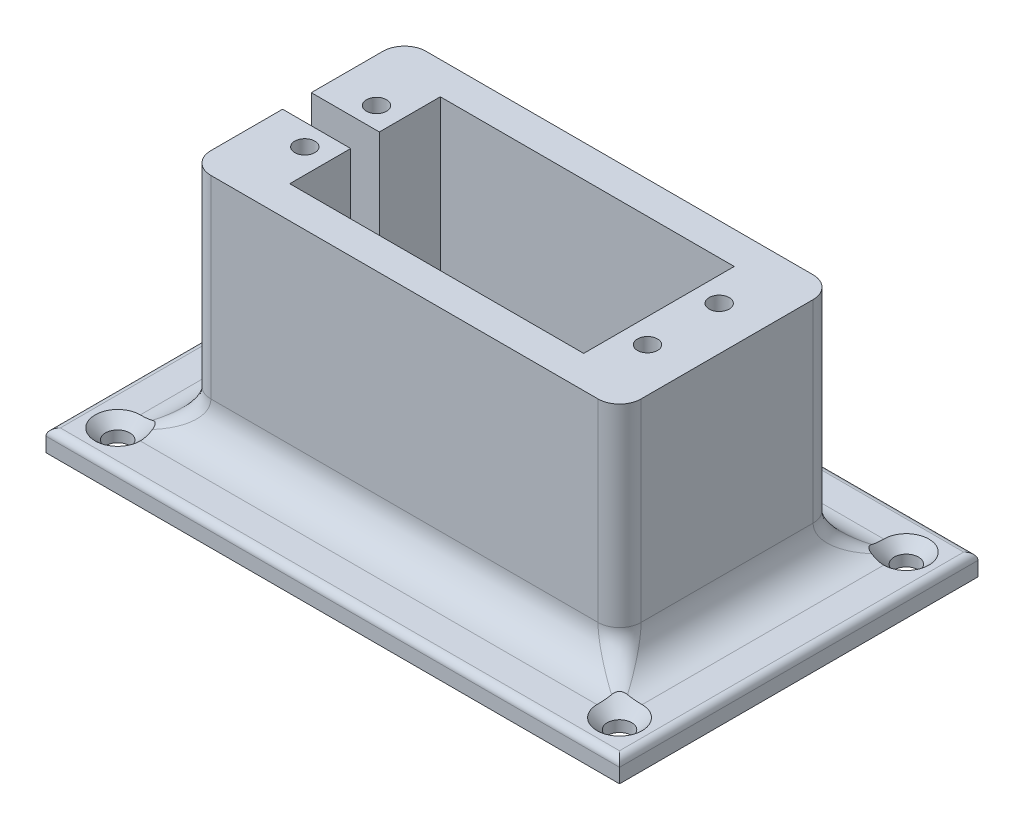
SolidWorks part; units mm, degrees
note: The reader was unsure of these and kept them because the rebuilt part matched: shared geometry of "Sketch1<4>", "Sketch1<5>".
ref_plane "Front Plane" through (0, 0, 0) normal (0, 0, 1) x (1, 0, 0)
ref_plane "Top Plane" through (0, 0, 0) normal (0, 1, 0) x (1, 0, 0)
ref_plane "Right Plane" through (0, 0, 0) normal (1, 0, 0) x (0, 0, -1)
sketch "Sketch1" plane through (0, 0, 0) normal (0, 1, 0) x (1, 0, 0)
  line L8 (0, 15) -> (60, 15) construction
  line L9 (0, 0) -> (60, 0)
  line L10 (0, 0) -> (0, 30)
  line L11 (0, 30) -> (60, 30)
  line L12 (60, 0) -> (60, 30)
  line L13 (30, 30) -> (30, 0) construction
  line L15 (9.5, 4.5) -> (50.5, 4.5)
  line L16 (9.5, 4.5) -> (9.5, 25.5)
  line L17 (9.5, 25.5) -> (50.5, 25.5)
  line L18 (50.5, 4.5) -> (50.5, 25.5)
  line L19 (9.5, 4.5) -> (50.5, 25.5) construction
  line L20 (9.5, 25.5) -> (50.5, 4.5) construction
  line L21 (-10, -10) -> (70, -10)
  line L22 (-10, -10) -> (-10, 40)
  line L23 (-10, 40) -> (70, 40)
  line L24 (70, -10) -> (70, 40)
  line L25 (-10, -10) -> (70, 40) construction
  line L26 (-10, 40) -> (70, -10) construction
  circle A0 centre (6.1, 20) radius 1.4
  circle A1 centre (53.9, 20) radius 1.4
  circle A2 centre (53.9, 10) radius 1.4
  circle A3 centre (6.1, 10) radius 1.4
  point P11 (30, 15)
  point P18 (30, 15)
  point P23 (30, 15)
  point P29 (0, 0)
  point P33 (0, 0)
  point P34 (0, 0)
  point P35 (0, 0)
  point P36 (0, 0)
  point P37 (0, 0)
  point P38 (0, 0)
  point P39 (0, 0)
  dimension "D3" = 2.8
  dimension "D1" = 60
  dimension "D2" = 30
  dimension "D4" = 10
  dimension "D5" = 47.8
  dimension "D6" = 41
  dimension "D7" = 21
  dimension "D8" = 50
  dimension "D9" = 80
extrude "Boss-Extrude2" add sketch "Sketch1" along normal blind 3 contours L21 L24 L23 L22 L12 L9 L10 L11
extrude "Boss-Extrude3" add sketch "Sketch1<4>" along normal blind 35 contours L9 L12 L11 L10 A1 A0 L18 L15 L16 L17 A2 A3
sketch "Sketch1<4>" plane through (0, 0, 0) normal (0, 1, 0) x (1, 0, 0) same geometry as "Sketch1"
extrude "Boss-Extrude4" add sketch "Sketch1<5>" along normal blind 25 contours A3 | A0 | A2 | A1
sketch "Sketch1<5>" plane through (0, 0, 0) normal (0, 1, 0) x (1, 0, 0) same geometry as "Sketch1"
sketch "Sketch2" plane through (0, 0, 0) normal (-1, 0, 0) x (0, 0, 1)
  line L0 (-17, 35) -> (-17, 12)
  line L1 (0, 35) -> (-30, 35) construction
  line L2 (-17, 12) -> (-18, 11)
  line L3 (-18, 11) -> (-18, 3)
  line L4 (0, 3) -> (-30, 3) construction
  line L5 (-15, 35) -> (-15, 3) construction
  line L6 (-12, 11) -> (-12, 3)
  line L7 (-13, 12) -> (-12, 11)
  line L8 (-13, 35) -> (-13, 12)
  line L9 (-17, 35) -> (-13, 35)
  line L10 (-18, 3) -> (-12, 3)
  dimension "D1" = 4
  dimension "D2" = 6
  dimension "D3" = 135
  dimension "D4" = 8
extrude "Cut-Extrude1" cut sketch "Sketch2" against normal up to next
sketch "Sketch8" plane through (0, 3, 0) normal (0, 1, 0) x (1, 0, 0)
  line L0 (-10, 40) -> (0, 30) construction
  line L1 (70, 40) -> (60, 30) construction
  line L2 (60, 0) -> (70, -10) construction
  line L3 (0, 0) -> (-10, -10) construction
hole_wizard "CSK for M3 Flat Head Machine Screw2" positions "3DSketch7" profile "Sketch10" countersink size "M3" standard "ANSI Metric" end condition up to next
sketch3d "3DSketch7"
  line L0 (70, 3, -40) -> (60, 3, -30) construction
  line L1 (-10, 3, -40) -> (0, 3, -30) construction
  line L2 (0, 3, 0) -> (-10, 3, 10) construction
  line L3 (60, 3, 0) -> (70, 3, 10) construction
  point P0 (-5, 3, 5)
  point P2 (65, 3, 5)
  point P4 (-5, 3, -35)
  point P6 (65, 3, -35)
  point P9 (0, 0, 0)
  point P12 (65, 3, -35)
  point P13 (0, 0, 0)
  point P16 (-5, 3, -35)
  point P17 (0, 0, 0)
  point P18 (0, 0, 0)
  point P21 (0, 0, 0)
sketch "Sketch10" plane through (-5, 3, 5) normal (1, 0, 0) x (0, 0, 1)
  line L0 (0, 0) -> (0, 3)
  line L1 (0, 3) -> (1.7, 3)
  line L2 (1.7, 3) -> (1.7, 1.45)
  line L3 (1.7, 1.45) -> (3.15, 0)
  line L5 (3.15, 0) -> (0, 0)
  line L6 (-1.7, 1.45) -> (-3.15, 0) construction
  line L11 (0, -6.35) -> (0, 107.95) construction
  dimension "Thru Hole Dia." = 3.4
  dimension "Thru Hole Depth" = 3
  dimension "Near C'Sink Dia." = 6.3
  dimension "Near C'Sink Angle" = 90
fillet "Fillet2" radius 5 5 edges at (60, 3, -15) (30, 3, -30) (0, 3, -24) (0, 3, -6) (30, 3, 0)
fillet "Fillet3" radius 3 8 edges at (60.5656, 5.6901, 0.5656) (60.5656, 5.6901, -30.5656) (-0.5656, 5.6901, 0.5656) (-0.5656, 5.6901, -30.5656) (60, 21.5, 0) (60, 21.5, -30) (0, 21.5, 0) (0, 21.5, -30)
fillet "Fillet4" radius 1 4 edges at (-10, 3, -15) (30, 3, -40) (70, 3, -15) (30, 3, 10)
fillet "Fillet5" radius 1 4 edges at (4.75, 11, -12) (4.75, 12, -13) (4.75, 11, -18) (4.75, 12, -17)
fillet "Fillet6" radius 1 2 edges at (2.25, 3, -12) (2.25, 3, -18)
